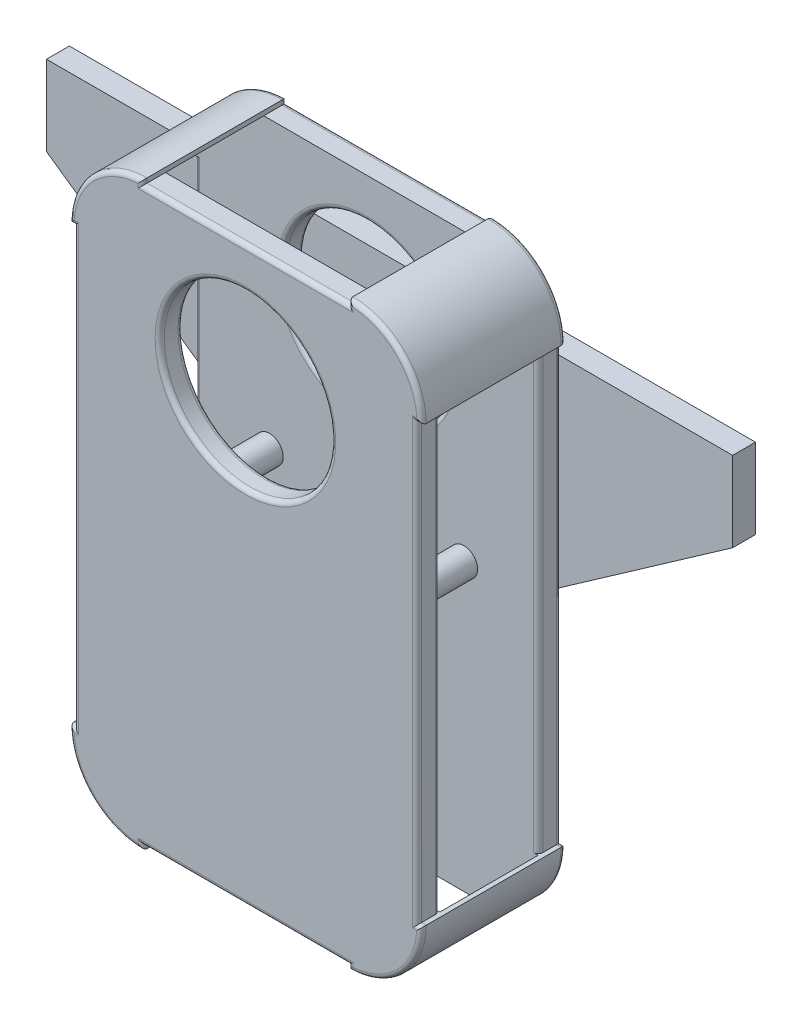
SolidWorks part; units mm, degrees
ref_plane "Front" through (0, 0, 0) normal (0, 0, 1) x (1, 0, 0)
ref_plane "Top" through (0, 0, 0) normal (0, 1, 0) x (1, 0, 0)
ref_plane "Right" through (0, 0, 0) normal (1, 0, 0) x (0, 0, -1)
sketch "Sketch2" plane through (0, 0, 0) normal (0, 0, 1) x (1, 0, 0)
  line L1 (-45, -125) -> (45, -125)
  line L2 (-75, -95) -> (-75, 95)
  line L3 (-45, 125) -> (45, 125)
  line L4 (75, -95) -> (75, 95)
  line L5 (-75, -125) -> (75, 125) construction
  line L6 (-75, 125) -> (75, -125) construction
  arc A0 (-45, -125) -> (-75, -95) centre (-45, -95) cw
  arc A1 (45, -125) -> (75, -95) centre (45, -95) ccw
  arc A2 (45, 125) -> (75, 95) centre (45, 95) cw
  arc A3 (-75, 95) -> (-45, 125) centre (-45, 95) cw
  point P0 (0, 0)
  dimension "D3" = 30
  dimension "D1" = 250
  dimension "D2" = 150
extrude "Boss-Extrude1" add sketch "Sketch2" along normal blind 10
ref_plane "Plane1" through (0, 0, -43) normal (0, 0, -1) x (-1, 0, 0)
sketch "Sketch4" plane through (0, 0, -43) normal (0, 0, -1) x (-1, 0, 0)
  line L4 (75, -95) -> (75, 95)
  line L5 (45, 125) -> (-45, 125)
  line L6 (-75, 95) -> (-75, -95)
  line L7 (-45, -125) -> (45, -125)
  line L8 (75, -95) -> (75, 95)
  line L9 (45, 125) -> (-45, 125)
  line L10 (-75, 95) -> (-75, -95)
  line L11 (-45, -125) -> (45, -125)
  arc A4 (45, -125) -> (75, -95) centre (45, -95) ccw
  arc A5 (75, 95) -> (45, 125) centre (45, 95) ccw
  arc A6 (-45, 125) -> (-75, 95) centre (-45, 95) ccw
  arc A7 (-75, -95) -> (-45, -125) centre (-45, -95) ccw
  arc A8 (45, -125) -> (75, -95) centre (45, -95) ccw
  arc A9 (75, 95) -> (45, 125) centre (45, 95) ccw
  arc A10 (-45, 125) -> (-75, 95) centre (-45, 95) ccw
  arc A11 (-75, -95) -> (-45, -125) centre (-45, -95) ccw
  dimension "D1" = 0
extrude "Boss-Extrude2" add sketch "Sketch4" along normal blind 10 separate body
sketch "Sketch5" plane through (0, 0, 10) normal (0, 0, 1) x (1, 0, 0)
  line L0 (45, 125) -> (-45, 125) construction
  circle A0 centre (0, 70) radius 37.5
  dimension "D1" = 75
  dimension "D2" = 55
extrude "Cut-Extrude1" cut sketch "Sketch5" against normal blind 170
fillet "Fillet1" radius 2 2 edges at (-37.5, 70, 0) (37.5, 70, 10)
fillet "Fillet2" radius 2 2 edges at (-37.5, 70, -43) (-37.5, 70, -53)
sketch "Sketch6" plane through (0, 0, -53) normal (0, 0, -1) x (-1, 0, 0)
  line L0 (-45, 127) -> (-45, 125)
  line L1 (-75, 95) -> (-77, 95)
  line L2 (45, 127) -> (45, 125)
  line L3 (75, 95) -> (77, 95)
  line L4 (77, -95) -> (75, -95)
  line L5 (45, -125) -> (45, -127)
  line L6 (-75, -95) -> (-77, -95)
  line L7 (-45, -125) -> (-45, -127)
  arc A0 (45, -125) -> (75, -95) centre (45, -95) ccw construction
  arc A1 (-75, -95) -> (-45, -125) centre (-45, -95) ccw construction
  arc A2 (75, 95) -> (45, 125) centre (45, 95) ccw construction
  arc A3 (-45, 125) -> (-75, 95) centre (-45, 95) ccw construction
  arc A4 (45, -125) -> (75, -95) centre (45, -95) ccw
  arc A5 (-75, -95) -> (-45, -125) centre (-45, -95) ccw
  arc A6 (75, 95) -> (45, 125) centre (45, 95) ccw
  arc A7 (-45, 125) -> (-75, 95) centre (-45, 95) ccw
  arc A8 (77, 95) -> (45, 127) centre (45, 95) ccw
  arc A9 (-45, 127) -> (-77, 95) centre (-45, 95) ccw
  arc A10 (-77, -95) -> (-45, -127) centre (-45, -95) ccw
  arc A11 (45, -127) -> (77, -95) centre (45, -95) ccw
  dimension "D1" = 2
extrude "Boss-Extrude3" add sketch "Sketch6" against normal up to surface (63 mm away) up to face at (-39.5, 70, 10)
fillet "Fillet3" radius 2 16 edges at (-76, 95, 10) (-67.6274, 117.6274, 10) (-45, 126, 10) (0, 125, 10) (45, 126, 10) (67.6274, 117.6274, 10) (76, 95, 10) (75, 0, 10) (76, -95, 10) (67.6274, -117.6274, 10) (45, -126, 10) (0, -125, 10) (-45, -126, 10) (-67.6274, -117.6274, 10) (-76, -95, 10) (-75, 0, 10)
fillet "Fillet4" radius 2 16 edges at (-67.6274, -117.6274, -53) (-45, -126, -53) (0, -125, -53) (45, -126, -53) (67.6274, -117.6274, -53) (76, -95, -53) (75, 0, -53) (76, 95, -53) (67.6274, 117.6274, -53) (45, 126, -53) (0, 125, -53) (-45, 126, -53) (-67.6274, 117.6274, -53) (-76, 95, -53) (-75, 0, -53) (-76, -95, -53)
fillet "Fillet8" radius 2 4 edges at (-75, 0, -43) (-75, 0, 0) (75, 0, 0) (75, 0, -43)
sketch "Sketch8" plane through (0, 0, 10) normal (0, 0, 1) x (1, 0, 0)
  circle A0 centre (42.5, 0) radius 6
  circle A1 centre (-42.5, 0) radius 6
  dimension "D1" = 12
extrude "Cut-Extrude4" cut sketch "Sketch8" against normal blind 101
sketch "Sketch19" plane through (0, 0, 10) normal (0, 0, 1) x (1, 0, 0)
  circle A0 centre (42.5, 0) radius 6 construction
  circle A1 centre (-42.5, 0) radius 6 construction
  circle A2 centre (42.5, 0) radius 6
  circle A3 centre (-42.5, 0) radius 6
extrude "Boss-Extrude11" add sketch "Sketch19" against normal through all separate body
ref_plane "Plane2" through (0, 0, 18) normal (0, 0, 1) x (1, 0, 0)
sketch "Sketch20" plane through (0, 0, -43) normal (0, 0, 1) x (1, 0, 0)
  line L0 (0, 0) -> (0, -141.1717) construction
  line L1 (-47, -123) -> (47, -123) construction
  circle A0 centre (0, -93.12) radius 6
  point P3 (0, -67.12)
  point P6 (0, -93.12)
  dimension "D3" = 12
  dimension "D1" = 55.88
  dimension "D2" = 26
extrude "Boss-Extrude12" add sketch "Sketch20" along normal up to surface (43 mm away) and the other way blind 10 up to face at (36.5, 0, 0)
sketch "Sketch21" plane through (0, 0, 0) normal (0, 0, -1) x (-1, 0, 0)
  line L2 (150, 88.916) -> (150, 53.916)
  line L3 (150, 53.916) -> (73, 0)
  line L4 (73, -97) -> (73, 97) construction
  line L5 (0, 0) -> (0, -48.7473) construction
  line L6 (-150, 53.916) -> (-73, 0)
  line L7 (-150, 88.916) -> (-150, 53.916)
  line L8 (-73, 0) -> (73, 0)
  line L10 (-150, 88.916) -> (150, 88.916)
  point P0 (0, 88.916)
  point P3 (5.8326, 88)
  dimension "D1" = 300
  dimension "D3" = 35
  dimension "D4" = 125
extrude "Boss-Extrude13" add sketch "Sketch21" against normal blind 10 from offset 63
